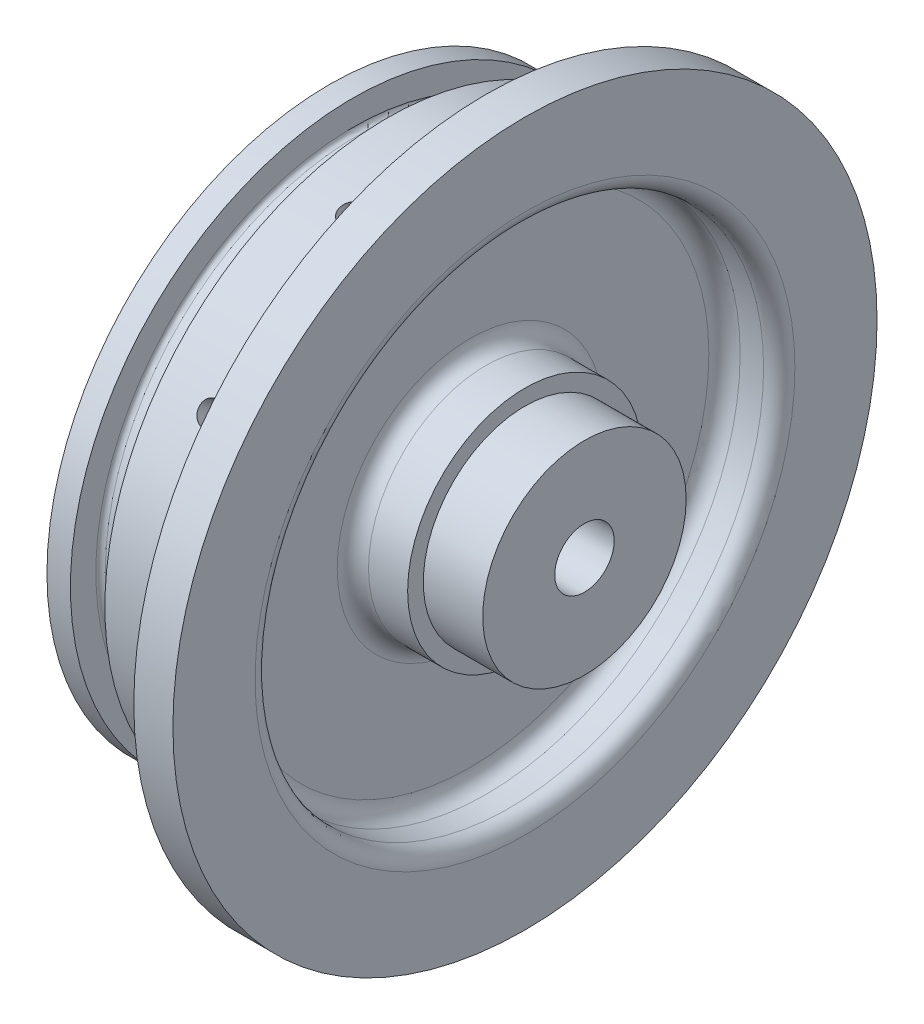
SolidWorks part; units mm, degrees
material "7075-T6 (SN)"
ref_plane "Front Plane" through (0, 0, 0) normal (0, 0, 1) x (1, 0, 0)
ref_plane "Top Plane" through (0, 0, 0) normal (0, 1, 0) x (1, 0, 0)
ref_plane "Right Plane" through (0, 0, 0) normal (1, 0, 0) x (0, 0, -1)
sketch "Sketch1" plane through (0, 0, 0) normal (1, 0, 0) x (0, 0, -1)
  circle A0 centre (0, 0) radius 57.15
  dimension "D1" = 114.3
extrude "Boss-Extrude1" add sketch "Sketch1" along normal blind 6.35
sketch "Sketch2" plane through (0, 0, 0) normal (-1, 0, 0) x (0, 0, 1)
  circle A0 centre (0, 0) radius 45.847
  dimension "D1" = 91.694
extrude "Boss-Extrude2" add sketch "Sketch2" along normal blind 25.4
sketch "Sketch10" plane through (0, 0, 0) normal (0, 1, 0) x (1, 0, 0)
  line L0 (0, 0) -> (-53.2238, 0) construction
  line L1 (-26.2636, 0) -> (26.2636, 0) construction
  line L2 (0, 0) -> (0, 64.5447) construction
  line L3 (0, -62.865) -> (0, 62.865) construction
ref_plane "Plane1" through (0, 0, -45.847) normal (0, 0, -1) x (-1, 0, 0)
sketch "Sketch11" plane through (0, 0, -45.847) normal (0, 0, -1) x (-1, 0, 0)
  line L0 (0, 0) -> (53.2238, 0) construction
  line L1 (0, -45.847) -> (0, 45.847) construction
  circle A0 centre (7.62, 0) radius 1.8986
  dimension "D2" = 3.7973
  dimension "D1" = 7.62
extrude "Cut-Extrude3" cut sketch "Sketch11" against normal blind 10.16
pattern_circular "CirPattern1" count 10 every 36 about axis through (0, 0, 0) along (-1, 0, 0) of "Cut-Extrude3" reverse direction yes
sketch "Sketch15" plane through (6.35, 0, 0) normal (1, 0, 0) x (0, 0, -1)
  circle A0 centre (0, 0) radius 4.826
  dimension "D1" = 9.652
extrude "Cut-Extrude4" cut sketch "Sketch15" against normal through all
sketch "Sketch16" plane through (0, 0, 0) normal (0, 0, 1) x (1, 0, 0)
  line L0 (0, 45.847) -> (-25.4, 45.847) construction
  line L1 (-21.59, 45.847) -> (-16.002, 45.847)
  line L2 (-21.59, 45.847) -> (-21.59, 41.7195)
  line L3 (-20.828, 40.9575) -> (-16.764, 40.9575)
  line L4 (-16.002, 45.847) -> (-16.002, 41.7195)
  line L5 (0, 0) -> (-53.2238, 0) construction
  line L6 (-25.4, 45.847) -> (-25.4, -45.847) construction
  arc A0 (-16.002, 41.7195) -> (-16.764, 40.9575) centre (-16.764, 41.7195) cw
  arc A1 (-20.828, 40.9575) -> (-21.59, 41.7195) centre (-20.828, 41.7195) cw
  point P8 (-26.6119, 0)
  point P13 (-16.002, 40.9575)
  point P16 (-21.59, 40.9575)
  dimension "D4" = 0.762
  dimension "D1" = 40.9575
  dimension "D2" = 3.81
  dimension "D3" = 5.588
revolve "Cut-Revolve1" cut sketch "Sketch16" angle 360 about L0
sketch "Sketch17" plane through (6.35, 0, 0) normal (1, 0, 0) x (0, 0, -1)
  circle A0 centre (0, 0) radius 16.51
  circle A1 centre (0, 0) radius 4.826
  dimension "D1" = 33.02
extrude "Boss-Extrude3" add sketch "Sketch17" along normal blind 9.652
sketch "Sketch18" plane through (0, 0, 0) normal (0, 0, 1) x (1, 0, 0)
  line L0 (6.35, -57.15) -> (6.35, 57.15) construction
  line L1 (6.35, 41.275) -> (-2.54, 41.275)
  line L2 (6.35, 41.275) -> (6.35, 19.05)
  line L3 (6.35, 19.05) -> (-2.54, 19.05)
  line L4 (-2.54, 41.275) -> (-2.54, 19.05)
  line L5 (0, 0) -> (-53.2238, 0) construction
  dimension "D1" = 8.89
  dimension "D2" = 19.05
  dimension "D3" = 41.275
revolve "Cut-Revolve2" cut sketch "Sketch18" angle 360 about L0
fillet "Fillet1" radius 2.54 3 edges at (6.35, 0, -41.275) (-2.54, 0, -41.275) (-2.54, 0, -19.05)
